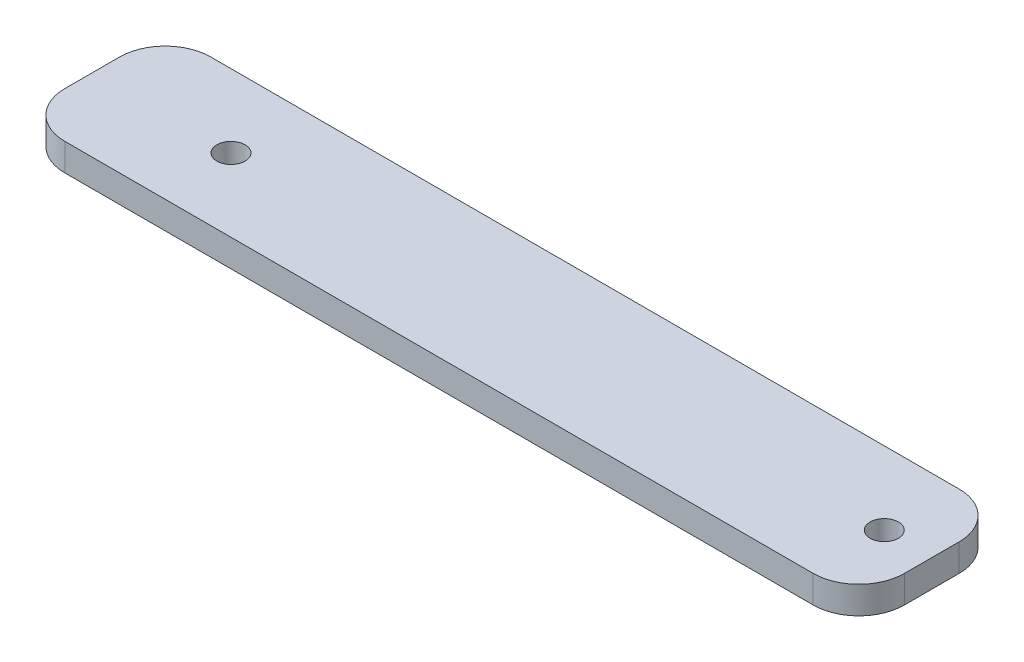
SolidWorks part; units mm, degrees
material "Nylon 101"
ref_plane "Front Plane" through (0, 0, 0) normal (0, 0, 1) x (1, 0, 0)
ref_plane "Top Plane" through (0, 0, 0) normal (0, 1, 0) x (1, 0, 0)
ref_plane "Right Plane" through (0, 0, 0) normal (1, 0, 0) x (0, 0, -1)
sketch "Sketch1" plane through (0, 0, 0) normal (0, 1, 0) x (1, 0, 0)
  line L0 (0, 0) -> (0, -275.7813) construction
  line L1 (0, 0) -> (81.58, 0) construction
  line L5 (-46, 8) -> (46, 8)
  line L8 (-46, -8) -> (46, -8)
  line L16 (46, 8) -> (46, -8)
  line L18 (-46, 8) -> (-46, -8)
  line L37 (5, -92.7422) -> (5, -214.7614) construction
  circle A36 centre (40.79, 0) radius 1.55
  circle A39 centre (-30.79, 0) radius 1.55
  dimension "D1" = 46
  dimension "D4" = 8
  dimension "D26" = 35.79
  dimension "D3" = 3.1
  dimension "D24" = 5
extrude "Boss-Extrude1" add sketch "Sketch1" along normal blind 3
fillet "Fillet1" radius 5 4 edges at (46, 1.5, -8) (-46, 1.5, -8) (-46, 1.5, 8) (46, 1.5, 8)
